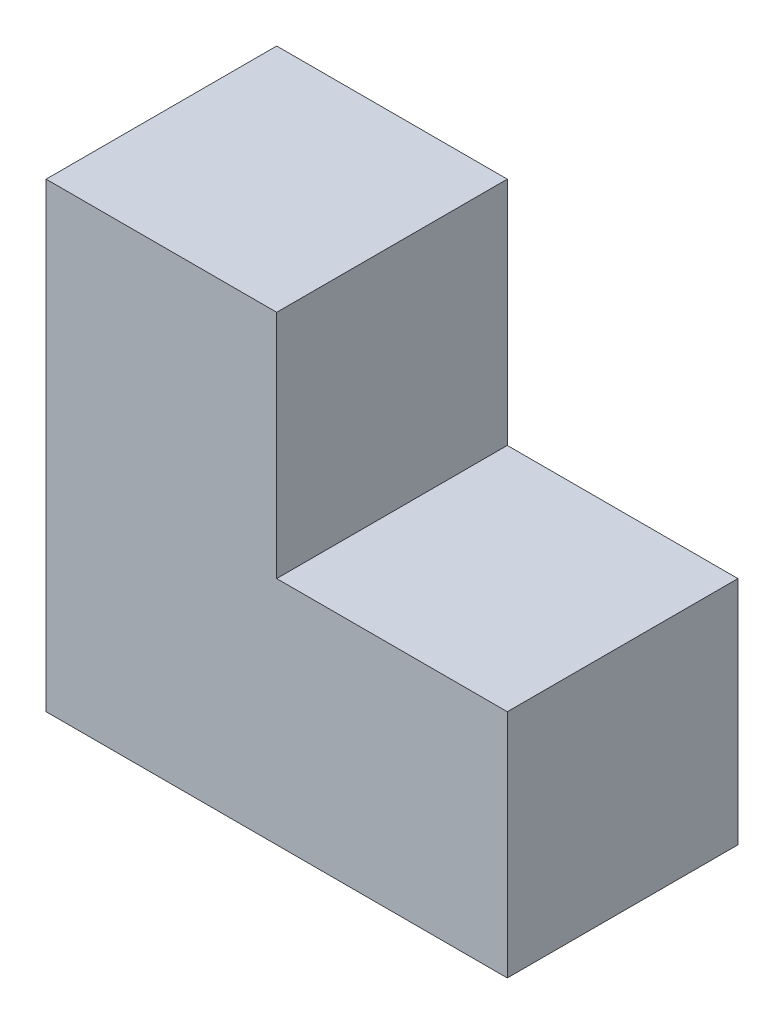
SolidWorks part; units mm, degrees
ref_plane "前基準面" through (0, 0, 0) normal (0, 0, 1) x (1, 0, 0)
ref_plane "上基準面" through (0, 0, 0) normal (0, 1, 0) x (1, 0, 0)
ref_plane "右基準面" through (0, 0, 0) normal (1, 0, 0) x (0, 0, -1)
ref_plane "平面1"
sketch "草圖1" plane through (0, 0, 0) normal (0, 0, 1) x (1, 0, 0)
  line L0 (0, 0) -> (60, 0)
  line L1 (60, 0) -> (60, 30)
  line L2 (60, 30) -> (30, 30)
  line L3 (30, 30) -> (30, 60)
  line L4 (30, 60) -> (0, 60)
  line L5 (0, 60) -> (0, 0)
  dimension "D1" = 60
  dimension "D2" = 30
  dimension "D3" = 30
  dimension "D4" = 30
  dimension "D5" = 30
extrude "擠出1" add sketch "草圖1" along normal blind 15 and the other way blind 15
